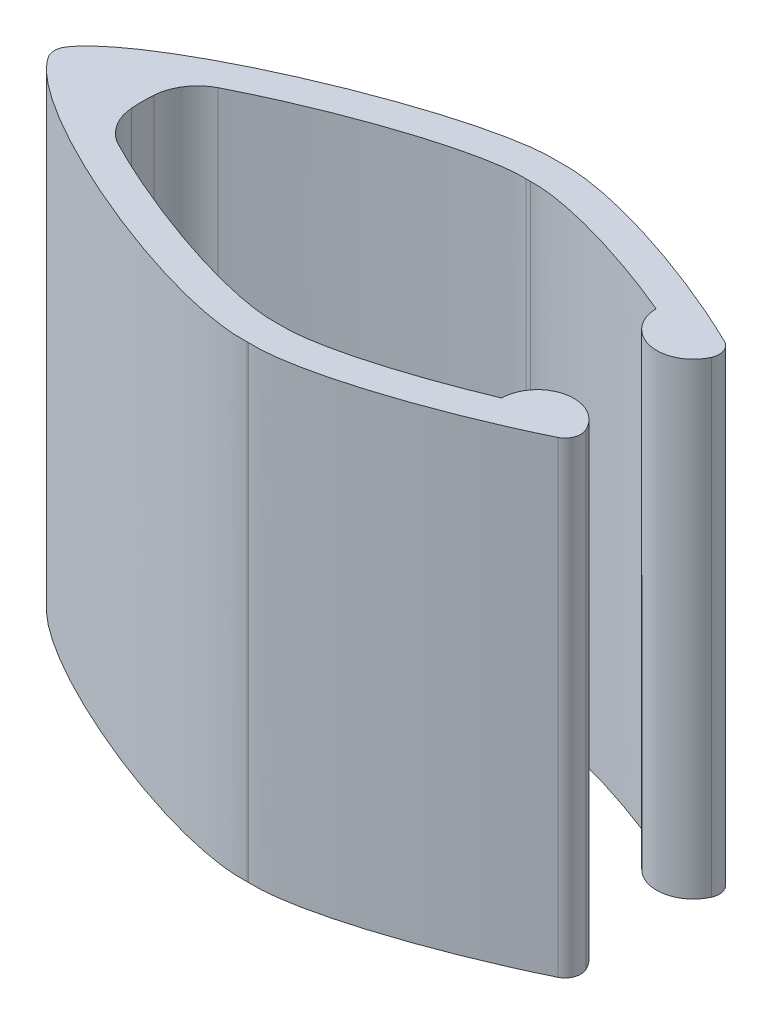
SolidWorks part; units mm, degrees
ref_plane "Front Plane" through (0, 0, 0) normal (0, 0, 1) x (1, 0, 0)
ref_plane "Top Plane" through (0, 0, 0) normal (0, 1, 0) x (1, 0, 0)
ref_plane "Right Plane" through (0, 0, 0) normal (1, 0, 0) x (0, 0, -1)
sketch "Sketch1" plane through (0, 0, 0) normal (0, 1, 0) x (1, 0, 0)
  line L0 (-11.25, 0) -> (11.25, 0)
  line L1 (-11.25, 0) -> (-11.25, 10) construction
  spline S0 degree 3 poles (-11.25, 10) (-5.7819, 10.3113) (10.2699, 3.4547) (11.25, 0) knots 0.45293 0.45293 0.45293 0.45293 1 1 1 1
  spline S1 degree 3 poles (-11.25, 10) (-16.7181, 10.3113) (-32.7699, 3.4547) (-33.75, 0) knots 0.45293 0.45293 0.45293 0.45293 1 1 1 1
  spline S2 degree 3 poles (-11.25, -10) (-5.7819, -10.3113) (10.2699, -3.4547) (11.25, 0) knots 0.45293 0.45293 0.45293 0.45293 1 1 1 1
  spline S3 degree 3 poles (-11.25, -10) (-16.7181, -10.3113) (-32.7699, -3.4547) (-33.75, 0) knots 0.45293 0.45293 0.45293 0.45293 1 1 1 1
  point P4 (0, 0)
  dimension "D1" = 22.5
  dimension "D2" = 10
extrude "Boss-Extrude1" add sketch "Sketch1" along normal blind 30 contours S2 S3 S1 S0
fillet "Fillet1" radius 1 4 edges at (-33.75, 15, 0) (-11.25, 15, -10) (11.25, 15, 0) (-11.25, 15, 10)
shell "Shell1" thickness 2 removed face at (-11.25, 0, 0) removed face at (-11.25, 30, 0)
sketch "Sketch3" plane through (0, 0, 0) normal (1, 0, 0) x (0, 0, -1)
  line L1 (-5, 30) -> (5, 30)
  line L2 (-5, 30) -> (-5, 0)
  line L3 (-5, 0) -> (5, 0)
  line L4 (5, 30) -> (5, 0)
  line L6 (-0.5401, 30) -> (-10.0103, 30) construction
  point P4 (-3.3328, 20)
  point P6 (0, 0)
  point P8 (0, 0)
  dimension "D1" = 10
extrude "Cut-Extrude1" cut sketch "Sketch3" along normal up to next
sketch "Sketch4" plane through (0, 30, 0) normal (0, 1, 0) x (1, 0, 0)
  line L0 (4.6836, 5) -> (0, 5) construction
  line L2 (4.6836, -5) -> (0, -5) construction
  circle A0 centre (2.3418, 5) radius 2.3418
  circle A1 centre (2.3418, -5) radius 2.3418
  spline S1 degree 3 poles (875.9109, -451.543) (-1033.6134, 465.4919) (1059.4253, -396.7665) (-950.4534, 301.1465) knots -1.161319 -1.161319 -1.161319 -1.161319 2.564681 2.564681 2.564681 2.564681 only from (-11.2014, 10.0026) to (4.6836, 5) construction
  spline S2 degree 3 poles (-11.2014, 10.0026) (-7.8576, 10.1653) (-0.6724, 7.719) (4.6836, 5) knots 0.454543 0.454543 0.454543 0.454543 0.785317 0.785317 0.785317 0.785317
  spline S3 degree 3 poles (875.9109, 451.543) (-1033.6134, -465.4919) (1059.4253, 396.7665) (-950.4534, -301.1465) knots -1.161319 -1.161319 -1.161319 -1.161319 2.564681 2.564681 2.564681 2.564681 only from (-11.2014, -10.0026) to (4.6836, -5) construction
  spline S4 degree 3 poles (-11.2014, -10.0026) (-7.8576, -10.1653) (-0.6724, -7.719) (4.6836, -5) knots 0.454543 0.454543 0.454543 0.454543 0.785317 0.785317 0.785317 0.785317
  line M3 (4.6836, -5) -> (0, -5)
  line M10 (0, 5) -> (4.6836, 5)
extrude "Boss-Extrude2" add sketch "Sketch4" against normal up to surface (30 mm away) contours A0 M10 | A1 M3 region at (2.3418, 30, -4.0061) region at (2.3418, 30, 4.0061) up to face at (-9.3698, 0, 0)
sketch "Sketch5" plane through (0, 30, 0) normal (0, 1, 0) x (1, 0, 0)
  circle A0 centre (-18, 0) radius 10
  spline S0 degree 3 poles (240.4687, 959.7553) (11.196, 5.2857) (-2.12, -8.6467) (-12.315, -7.9792) (-12.5408, -7.9557) (-13.2148, -7.8692) (-14.548, -7.6326) (-15.8566, -7.2888) (-17.5895, -6.7786) (-18.4497, -6.4961) (-20.1606, -5.8898) (-21.008, -5.5669) (-22.6875, -4.8854) (-23.5199, -4.5267) (-25.1684, -3.7711) (-25.9856, -3.3738) (-27.5901, -2.5343) (-28.3789, -2.0928) (-29.5271, -1.374) (-29.904, -1.1248) (-41.8797, 7.5167) (-45.3112, 29.1213) (458.7427, 871.6769) knots -1.335848 -1.335848 -1.335848 -1.335848 0.03125 0.03125 0.0625 0.0625 0.125 0.25 0.25 0.375 0.375 0.5 0.5 0.625 0.625 0.75 0.75 0.875 0.875 0.9375 0.9375 2.913869 2.913869 2.913869 2.913869 only from (-11.3959, -8.0049) to (-31.3321, 0) construction
  spline S1 degree 3 poles (240.4687, -959.7553) (11.196, -5.2857) (-2.12, 8.6467) (-12.315, 7.9792) (-12.5408, 7.9557) (-13.2148, 7.8692) (-14.548, 7.6326) (-15.8566, 7.2888) (-17.5895, 6.7786) (-18.4497, 6.4961) (-20.1606, 5.8898) (-21.008, 5.5669) (-22.6875, 4.8854) (-23.5199, 4.5267) (-25.1684, 3.7711) (-25.9856, 3.3738) (-27.5901, 2.5343) (-28.3789, 2.0928) (-29.5271, 1.374) (-29.904, 1.1248) (-41.8797, -7.5167) (-45.3112, -29.1213) (458.7427, -871.6769) knots -1.335848 -1.335848 -1.335848 -1.335848 0.03125 0.03125 0.0625 0.0625 0.125 0.25 0.25 0.375 0.375 0.5 0.5 0.625 0.625 0.75 0.75 0.875 0.875 0.9375 0.9375 2.913869 2.913869 2.913869 2.913869 only from (-11.3959, 8.0049) to (-31.3321, 0) construction
  spline S2 degree 3 poles (-11.3959, 8.0049) (-11.6297, 8.0163) (-11.8593, 8.009) (-12.315, 7.9792) (-12.5408, 7.9557) (-13.2148, 7.8692) (-14.548, 7.6326) (-15.8566, 7.2888) (-17.5895, 6.7786) (-18.4497, 6.4961) (-20.1606, 5.8898) (-21.008, 5.5669) (-22.6875, 4.8854) (-23.5199, 4.5267) (-25.1684, 3.7711) (-25.9856, 3.3738) (-27.5901, 2.5343) (-28.3789, 2.0928) (-29.5271, 1.374) (-29.904, 1.1248) (-30.6382, 0.595) (-30.9971, 0.3169) (-31.3321, 0) knots 0 0 0 0 0.03125 0.03125 0.0625 0.0625 0.125 0.25 0.25 0.375 0.375 0.5 0.5 0.625 0.625 0.75 0.75 0.875 0.875 0.9375 0.9375 1 1 1 1
  spline S3 degree 3 poles (-11.3959, -8.0049) (-11.6297, -8.0163) (-11.8593, -8.009) (-12.315, -7.9792) (-12.5408, -7.9557) (-13.2148, -7.8692) (-14.548, -7.6326) (-15.8566, -7.2888) (-17.5895, -6.7786) (-18.4497, -6.4961) (-20.1606, -5.8898) (-21.008, -5.5669) (-22.6875, -4.8854) (-23.5199, -4.5267) (-25.1684, -3.7711) (-25.9856, -3.3738) (-27.5901, -2.5343) (-28.3789, -2.0928) (-29.5271, -1.374) (-29.904, -1.1248) (-30.6382, -0.595) (-30.9971, -0.3169) (-31.3321, 0) knots 0 0 0 0 0.03125 0.03125 0.0625 0.0625 0.125 0.25 0.25 0.375 0.375 0.5 0.5 0.625 0.625 0.75 0.75 0.875 0.875 0.9375 0.9375 1 1 1 1
  point P2 (0, 0)
  dimension "D2" = 20
  dimension "D1" = 18
extrude "Boss-Extrude4" add sketch "Sketch5" against normal up to surface (30 mm away) contours A0 region at (-29.0947, 30, 0) up to face at (-9.6453, 0, 0)
fillet "Fillet2" radius 3 2 edges
fillet "Fillet3" radius 1 2 edges
equation "\"Length\"= 45"
equation "\"Width\"= 20"
equation "\"D1@Sketch1\"=\"Length\"/2"
equation "\"D2@Sketch1\"=\"Width\"/2"
equation "\"Height\"= 30"
equation "\"D1@Boss-Extrude1\"=\"Height\""
equation "\"D2@Sketch5\"=\"Width\""
equation "\"D1@Sketch5\"=\"Length\"*0.4"
equation "\"D1@Sketch3\"=\"Width\"/2"
